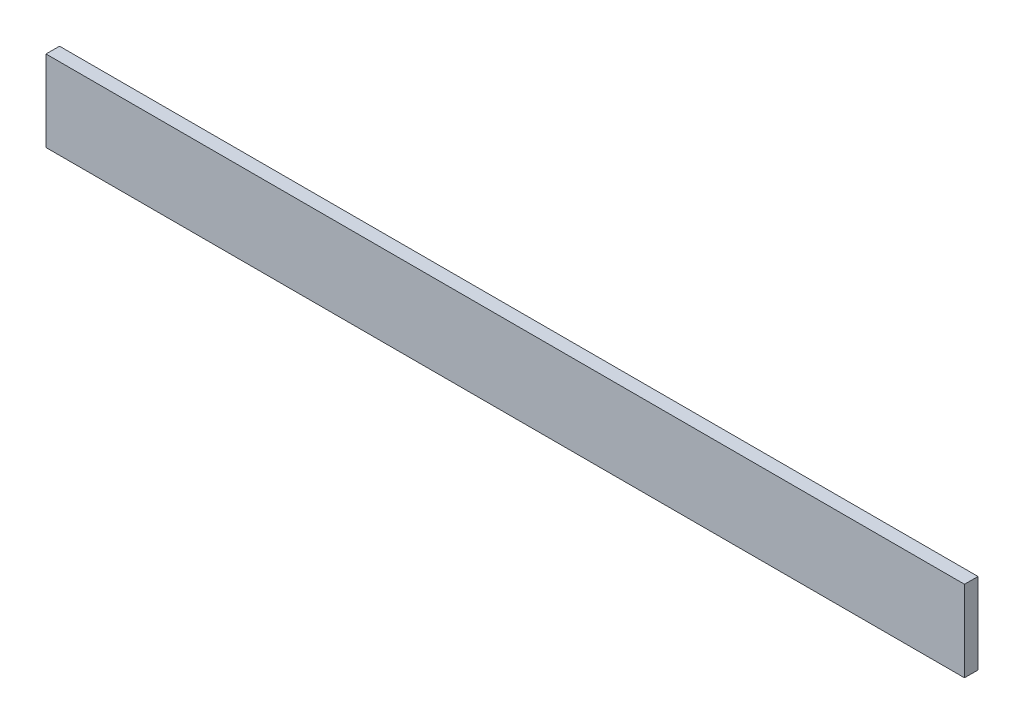
SolidWorks part; units mm, degrees
ref_plane "Front Plane" through (0, 0, 0) normal (0, 0, 1) x (1, 0, 0)
ref_plane "Top Plane" through (0, 0, 0) normal (0, 1, 0) x (1, 0, 0)
ref_plane "Right Plane" through (0, 0, 0) normal (1, 0, 0) x (0, 0, -1)
sketch "Sketch1" plane through (0, 0, 0) normal (0, 0, 1) x (1, 0, 0)
  line L1 (0, 0) -> (431.8, 0)
  line L2 (0, 0) -> (0, 38.1)
  line L3 (0, 38.1) -> (431.8, 38.1)
  line L4 (431.8, 0) -> (431.8, 38.1)
  dimension "D1" = 38.1
  dimension "D2" = 431.8
extrude "Boss-Extrude1" add sketch "Sketch1" along normal blind 6.35
move or copy body "Body-Move/Copy1" [suppressed] bodies to move or copy 101 parameters "D1"=0, "D2"=0, "D3"=0
